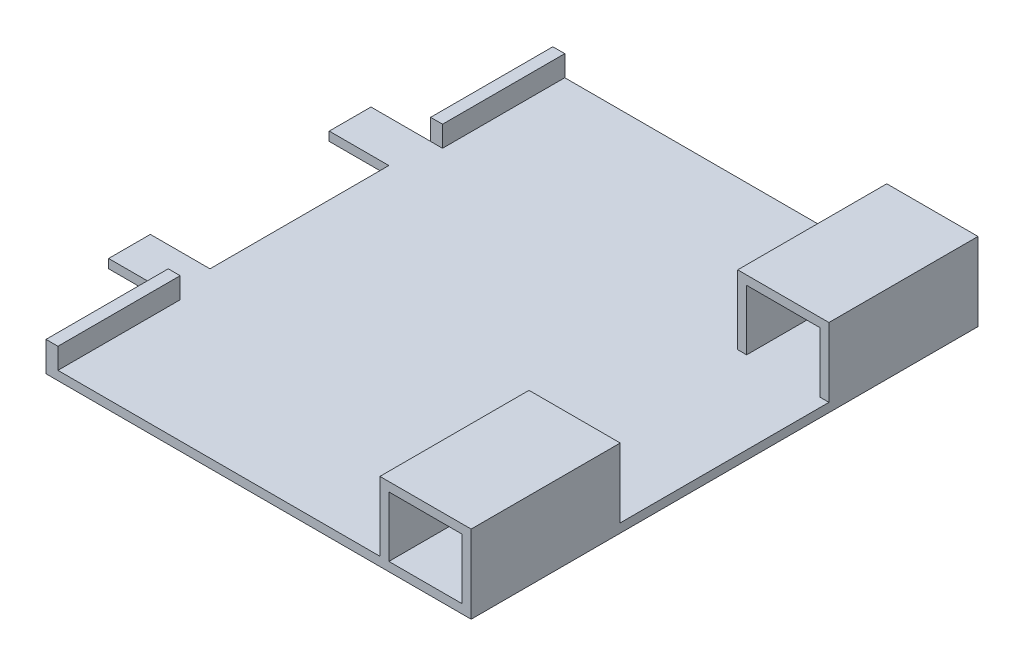
SolidWorks part; units mm, degrees
ref_plane "Front Plane" through (0, 0, 0) normal (0, 0, 1) x (1, 0, 0)
ref_plane "Top Plane" through (0, 0, 0) normal (0, 1, 0) x (1, 0, 0)
ref_plane "Right Plane" through (0, 0, 0) normal (1, 0, 0) x (0, 0, -1)
sketch "Sketch1" plane through (0, 0, 0) normal (0, 1, 0) x (1, 0, 0)
  line L5 (-6.5, 70) -> (64.8, 70)
  line L6 (-6.5, 70) -> (-6.5, -15)
  line L7 (-6.5, -15) -> (64.8, -15)
  line L8 (64.8, 70) -> (64.8, -15)
  line L11 (64.8, 70) -> (64.8, 45)
  line L14 (64.8, -15) -> (53.8, -15)
  line L15 (64.8, -15) -> (64.8, 10)
  line L44 (-6.5, 42.5) -> (-16.5, 42.5) construction
  line L45 (49.5, 70) -> (60.5, 70)
  line L49 (21.3, -15) -> (32.3, -15)
  line L54 (-6.5, 70) -> (-6.5, -15)
  line L57 (-16.5, 12.5) -> (-6.5, 12.5) construction
  line L58 (63.3, -15) -> (63.3, 10)
  line L59 (-16.5, 12.5) -> (-6.5, 12.5)
  line L61 (-6.5, 5.5) -> (-6.5, -15)
  line L64 (-16.5, 49.5) -> (-16.5, 42.5)
  line L65 (-16.5, 42.5) -> (-6.5, 42.5)
  line L66 (-6.5, 42.5) -> (-6.5, 49.5)
  line L67 (-6.5, 49.5) -> (-6.5, 70)
  line L68 (-16.5, 5.5) -> (-16.5, 12.5)
  line L69 (-16.5, 12.5) -> (-6.5, 12.5)
  line L70 (-6.5, 12.5) -> (-6.5, -15)
  line L71 (-16.5, 12.5) -> (-16.5, 5.5)
  line L72 (-16.5, 5.5) -> (-6.5, 5.5)
  line L73 (-6.5, 12.5) -> (-6.5, 5.5)
  line L74 (-16.5, 42.5) -> (-6.5, 42.5)
  line L75 (-16.5, 42.5) -> (-16.5, 49.5)
  line L76 (-16.5, 49.5) -> (-6.5, 49.5)
  line L77 (-6.5, 42.5) -> (-6.5, 49.5)
  line L78 (64.8, -15) -> (52.3, -15)
  line L79 (64.8, -15) -> (64.8, 11.5)
  line L82 (59.1961, -15) -> (47.4334, -15)
  line L86 (63.3, 70) -> (63.3, 45)
  line L87 (51, -15) -> (51, 10)
  line L88 (51, 70) -> (51, 45)
  line L89 (49.5, 70) -> (49.5, 45)
  line L90 (51, 10) -> (49.5, 10)
  line L91 (49.5, 45) -> (51, 45)
  line L92 (63.3, 45) -> (64.8, 45)
  line L93 (49.5, 10) -> (49.5, -15)
  line L94 (63.3, 10) -> (64.8, 10)
  line L95 (-4.5, 70) -> (-4.5, 49.5)
  line L96 (-4.5, 49.5) -> (-6.5, 49.5)
  line L97 (-4.5, -15) -> (-4.5, 5.5)
  line L98 (-4.5, 5.5) -> (-6.5, 5.5)
  point P4 (0, 0)
  point P10 (0, 0)
  point P50 (-6.5, 27.5)
  dimension "D2" = 56
  dimension "D4" = 85
  dimension "D7" = 2
  dimension "D8" = 2
  dimension "D9" = 1.5
  dimension "D10" = 1.5
  dimension "D45" = 7
  dimension "D46" = 30
  dimension "D47" = 15
  dimension "D48" = 7
  dimension "D49" = 10
  dimension "D50" = 10
  dimension "D51" = 25
  dimension "D52" = 13.8
  dimension "D53" = 12.3
  dimension "D54" = 12.3
  dimension "D55" = 1.5
  dimension "D56" = 25
  dimension "D57" = 25
extrude "Boss-Extrude2" add sketch "Sketch1" along normal blind 1.5 contours L58 L94 L8 L92 L86 L5 L88 L91 L89 L6 L54 L7 L78 region at (28.9169, 0, -27.5)
extrude "Boss-Extrude3" add sketch "Sketch1<4>" along normal blind 1.5 contours L76 L64 L65 L54 | L68 L72 L54 L59 region at (-11.5, 0, -46) region at (-11.5, 0, -9)
sketch "Sketch1<4>" plane through (0, 0, 0) normal (0, 1, 0) x (1, 0, 0) same geometry as "Sketch1"
extrude "Boss-Extrude11" add sketch "Sketch1<14>" along normal blind 5 contours L96 L95 L5 L6 | L97 L98 L6 L7 region at (-5.5, 0, -59.75) region at (-5.5, 0, 4.75)
sketch "Sketch1<14>" plane through (0, 0, 0) normal (0, 1, 0) x (1, 0, 0) same geometry as "Sketch1"
extrude "Boss-Extrude12" add sketch "Sketch1<16>" along normal blind 11.6 contours L90 L93 L82 L87 | L94 L58 L14 L8 | L86 L92 L8 L5 | L89 L91 L88 L5 region at (50.25, 0, -57.5) region at (64.05, 0, -57.5) region at (64.05, 0, 2.5) region at (50.25, 0, 2.5)
sketch "Sketch1<16>" plane through (0, 0, 0) normal (0, 1, 0) x (1, 0, 0) same geometry as "Sketch1"
sketch "Sketch2" plane through (0, 11.6, 0) normal (0, 1, 0) x (1, 0, 0)
  line L1 (49.5, 70) -> (64.8, 70)
  line L2 (49.5, 70) -> (49.5, 45)
  line L3 (49.5, 45) -> (64.8, 45)
  line L4 (64.8, 70) -> (64.8, 45)
  line L5 (49.5, 10) -> (64.8, 10)
  line L6 (49.5, 10) -> (49.5, -15)
  line L7 (49.5, -15) -> (64.8, -15)
  line L8 (64.8, 10) -> (64.8, -15)
extrude "Boss-Extrude13" add sketch "Sketch2" along normal blind 1.5
ref_plane "Plane1" through (51, 11.6, 15) normal (1, 0, 0) x (0, 0, -1)
